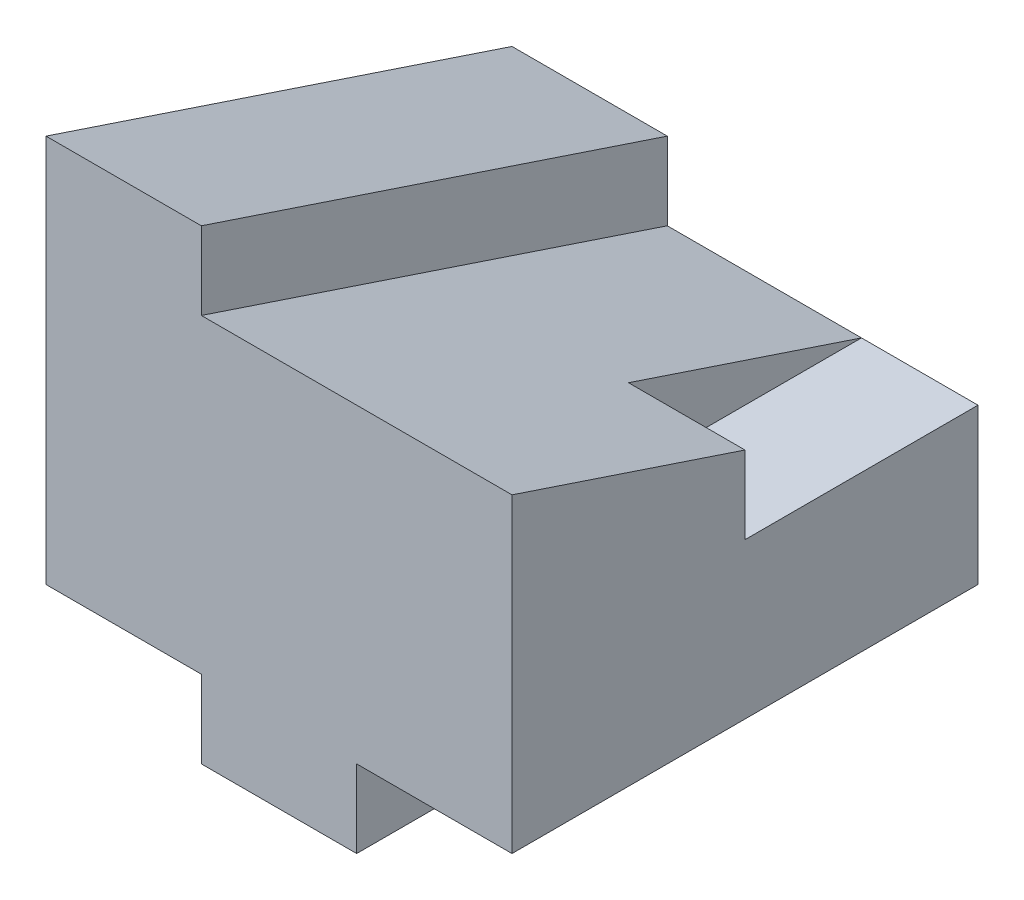
SolidWorks part; units mm, degrees
ref_plane "Front Plane" through (0, 0, 0) normal (0, 0, 1) x (1, 0, 0)
ref_plane "Top Plane" through (0, 0, 0) normal (0, 1, 0) x (1, 0, 0)
ref_plane "Right Plane" through (0, 0, 0) normal (1, 0, 0) x (0, 0, -1)
sketch "Sketch1" plane through (0, 0, 0) normal (1, 0, 0) x (0, 0, -1)
  line L0 (0, 40) -> (0, 0)
  line L1 (0, 0) -> (60, 0)
  line L2 (60, 0) -> (60, 20)
  line L3 (60, 20) -> (0, 40)
  line L4 (0, 50) -> (60, 30)
  line L5 (60, 30) -> (60, 20)
  line L6 (0, 50) -> (0, 40)
  line L7 (30, 30) -> (30, 20)
  line L8 (30, 20) -> (60, 20)
  line L9 (0, 0) -> (0, -10)
  line L10 (0, -10) -> (60, -10)
  line L11 (60, -10) -> (60, 0)
  dimension "D1" = 50
  dimension "D2" = 40
  dimension "D3" = 20
  dimension "D4" = 60
  dimension "D5" = 30
  dimension "D6" = 10
extrude "Boss-Extrude7" add sketch "Sketch1" along normal blind 25 contours L7 L8 L3 region at (0, 23.3333, -40)
extrude "Boss-Extrude8" add sketch "Sketch1<12>" along normal blind 20 separate body contours L10 L11 L1 L9 region at (0, -5, -30)
sketch "Sketch1<12>" plane through (0, 0, 0) normal (1, 0, 0) x (0, 0, -1) same geometry as "Sketch1"
extrude "Boss-Extrude9" add sketch "Sketch1<13>" along normal blind 40 contours L8 L7 L3 L0 L1 L2 region at (0, 14.8485, -25.4545)
sketch "Sketch1<13>" plane through (0, 0, 0) normal (1, 0, 0) x (0, 0, -1) same geometry as "Sketch1"
extrude "Boss-Extrude10" add sketch "Sketch1<14>" against normal blind 20 contours L4 L6 L3 L5 | L8 L7 L3 L0 L1 L2 | L7 L8 L3 region at (0, 14.8485, -25.4545) region at (0, 35, -30) region at (0, 23.3333, -40)
sketch "Sketch1<14>" plane through (0, 0, 0) normal (1, 0, 0) x (0, 0, -1) same geometry as "Sketch1"
